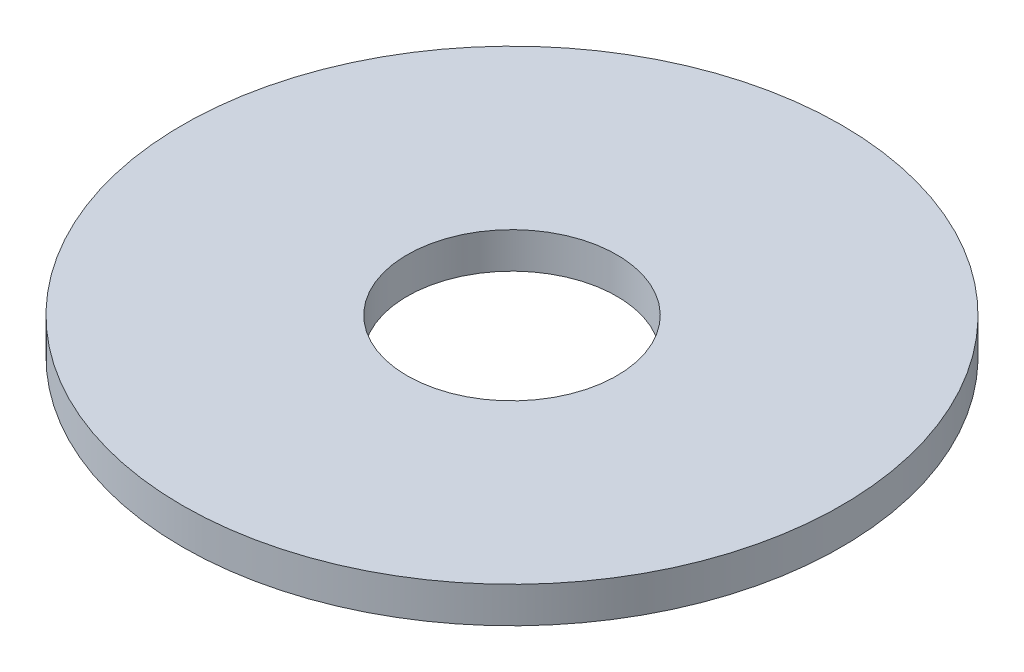
SolidWorks part; units mm, degrees
ref_plane "Front Plane" through (0, 0, 0) normal (0, 0, 1) x (1, 0, 0)
ref_plane "Top Plane" through (0, 0, 0) normal (0, 1, 0) x (1, 0, 0)
ref_plane "Right Plane" through (0, 0, 0) normal (1, 0, 0) x (0, 0, -1)
sketch "Sketch1" plane through (0, 0, 0) normal (0, 1, 0) x (1, 0, 0)
  circle A0 centre (0, 0) radius 55
  dimension "FLANGE_OD" = 110
extrude "Boss-Extrude1" add sketch "Sketch1" along normal blind 6
sketch "Sketch2" plane through (0, 0, 0) normal (0, 1, 0) x (1, 0, 0)
  circle A0 centre (0, 0) radius 17.5
  dimension "BORE_D" = 35
extrude "Cut-Extrude1" cut sketch "Sketch2" along normal through all
sketch "Sketch3" plane through (0, 6, 0) normal (0, 1, 0) x (1, 0, 0)
  circle A0 centre (0, 0) radius 13.237 construction
  circle A1 centre (-13.237, 0) radius 1.6426
  dimension "BOLT_D" = 3.2852
  dimension "BOLT_PCD" = 26.474
extrude "Cut-Extrude2" cut sketch "Sketch3" against normal blind 4.52 rebuild error yes
pattern_circular "CirPattern1" count 3 over 360 rebuild error yes
